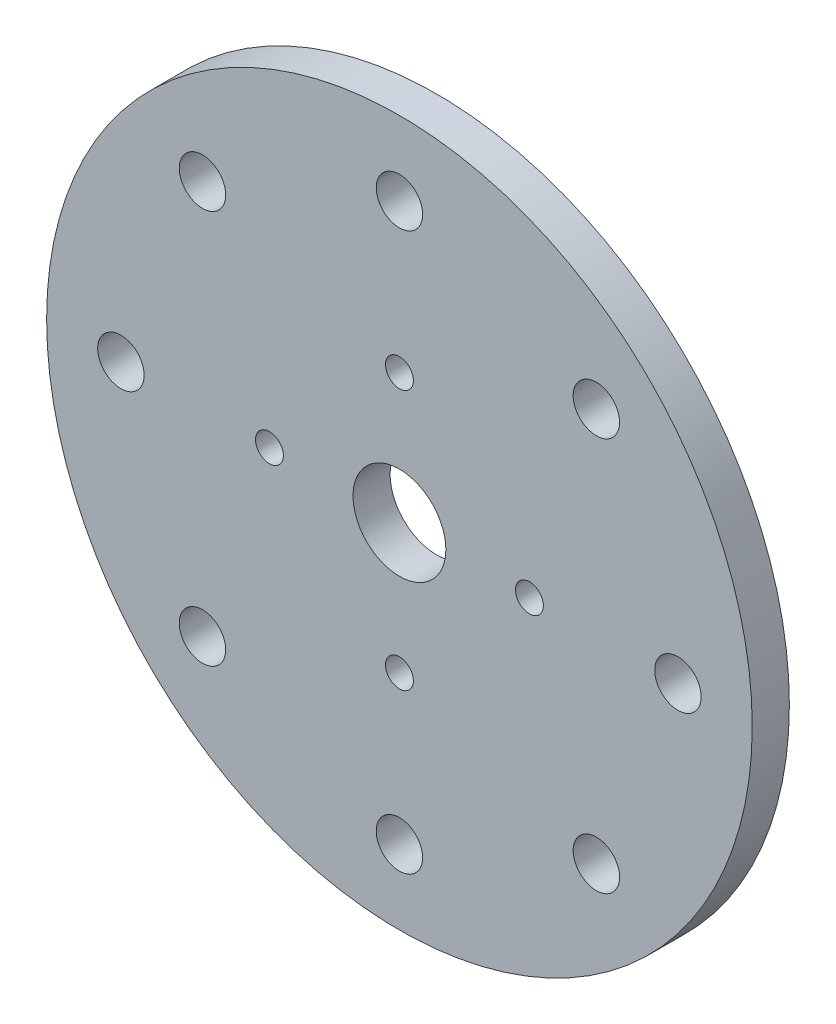
SolidWorks part; units mm, degrees
ref_plane "前视基准面" through (0, 0, 0) normal (0, 0, 1) x (1, 0, 0)
ref_plane "上视基准面" through (0, 0, 0) normal (0, 1, 0) x (1, 0, 0)
ref_plane "右视基准面" through (0, 0, 0) normal (1, 0, 0) x (0, 0, -1)
ref_axis "x轴" through (88.99, 0, 0) along (-1, 0, 0)
ref_axis "y轴" through (0, 0, -88.99) along (0, 0, 1)
ref_axis "z轴" through (0, -44, 0) along (0, 1, 0)
sketch "草图1" plane through (0, 0, 0) normal (0, 0, 1) x (1, 0, 0)
  circle A0 centre (0, 0) radius 14 construction
  circle A1 centre (0, 0) radius 38
  circle A2 centre (0, 0) radius 5
  circle A3 centre (0, 0) radius 30 construction
  circle A4 centre (0, 30) radius 2.5
  circle A5 centre (21.2132, 21.2132) radius 2.5
  circle A6 centre (30, 0) radius 2.5
  circle A7 centre (21.2132, -21.2132) radius 2.5
  circle A8 centre (0, -30) radius 2.5
  circle A9 centre (-21.2132, -21.2132) radius 2.5
  circle A10 centre (-30, 0) radius 2.5
  circle A11 centre (-21.2132, 21.2132) radius 2.5
  circle A12 centre (0, 14) radius 1.5
  circle A13 centre (14, 0) radius 1.5
  circle A14 centre (0, -14) radius 1.5
  circle A15 centre (-14, 0) radius 1.5
  point P24 (0, 0)
  point P34 (0, 0)
  dimension "D1" = 8
  dimension "D2" = 4
extrude "凸台-拉伸2" add sketch "草图1" along normal blind 4
